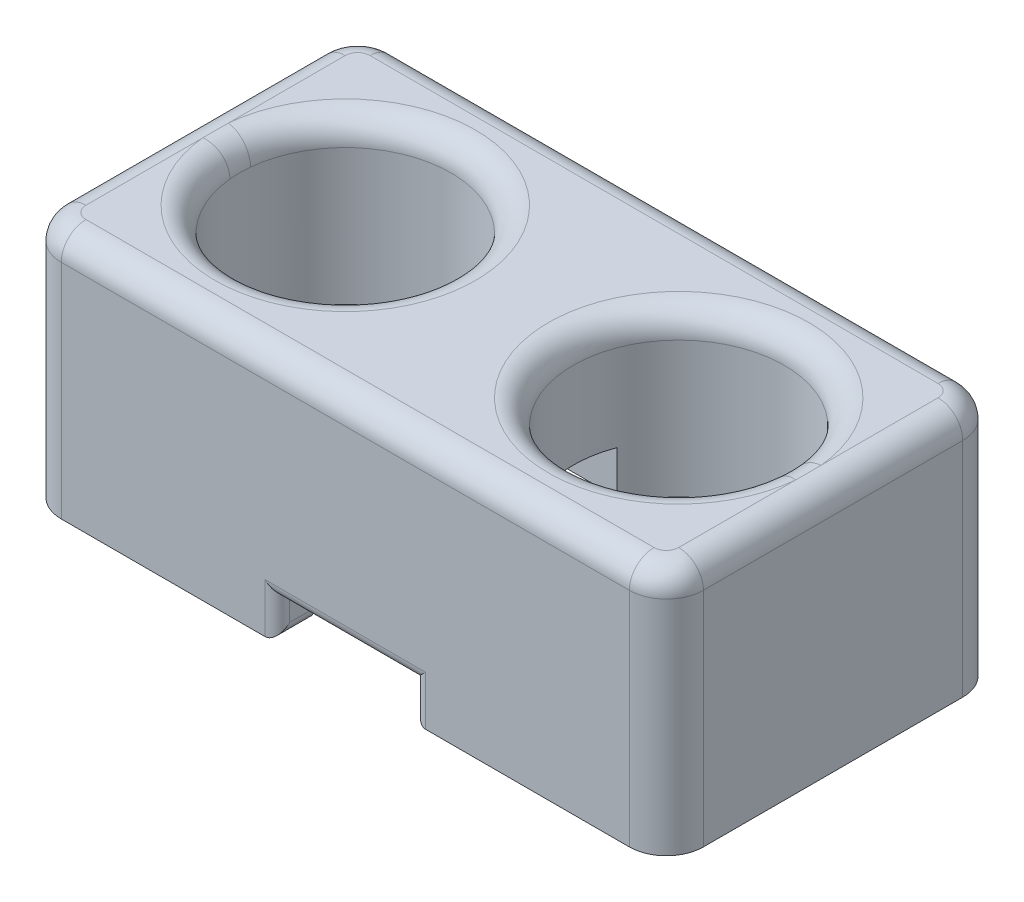
SolidWorks part; units mm, degrees
ref_plane "Front Plane" through (0, 0, 0) normal (0, 0, 1) x (1, 0, 0)
ref_plane "Top Plane" through (0, 0, 0) normal (0, 1, 0) x (1, 0, 0)
ref_plane "Right Plane" through (0, 0, 0) normal (1, 0, 0) x (0, 0, -1)
sketch "Sketch1" plane through (0, 0, 0) normal (0, 1, 0) x (1, 0, 0)
  line L0 (-23, -0.2538) -> (23, -0.2538) construction
  line L1 (-23, -10.7538) -> (23, -10.7538)
  line L2 (-23, -10.7538) -> (-23, 10.2462)
  line L3 (-23, 10.2462) -> (23, 10.2462)
  line L4 (23, -10.7538) -> (23, 10.2462)
  line L5 (0, 10.2462) -> (0, -10.7538) construction
  line L7 (5.5, 10.2462) -> (-5.5, 10.2462)
  line L8 (5.5, 10.2462) -> (5.5, -10.7538)
  line L9 (5.5, -10.7538) -> (-5.5, -10.7538)
  line L10 (-5.5, 10.2462) -> (-5.5, -10.7538)
  line L11 (-26, 13.2462) -> (26, 13.2462)
  line L12 (-26, 13.2462) -> (-26, -13.7538)
  line L13 (-26, -13.7538) -> (26, -13.7538)
  line L14 (26, 13.2462) -> (26, -13.7538)
  line L15 (5.5, -10.7538) -> (-5.5, -10.7538)
  line L16 (5.5, -10.7538) -> (5.5, -13.7538)
  line L17 (5.5, -13.7538) -> (-5.5, -13.7538)
  line L18 (-5.5, -10.7538) -> (-5.5, -13.7538)
  circle A0 centre (-13.5, -0.2538) radius 8.55
  circle A1 centre (13.5, -0.2538) radius 8.55
  point P0 (0, 0)
  dimension "D3" = 17.1
  dimension "D4" = 17.5
  dimension "D10" = 9.5
  dimension "D11" = 9.5
  dimension "D1" = 21
  dimension "D2" = 46
  dimension "D5" = 11
  dimension "D6" = 3
  dimension "D7" = 3
  dimension "D8" = 3
  dimension "D9" = 3
extrude "Boss-Extrude1" add sketch "Sketch1" along normal blind 20 contours L14 L11 L12 L13 L4 L1 L2 L3 | L10 A0 L3 L2 L1 | L3 L10 L1 L8 | L8 A1 L1 L4 L3 | L1 L18 L13 L16 | A0 | A1 region at (-22.7266, 0, 0.2538) region at (-14.25, 0, 11.3397) region at (0, 0, 0.2538) region at (0, 0, 12.2538) region at (5.7734, 0, 7.0123) region at (-13.5805, 0, 0.2538) region at (13.5805, 0, 0.2538)
extrude "Cut-Extrude1" cut sketch "Sketch1<3>" along normal blind 3 contours L1 L18 L13 L16 region at (0, 0, 12.2538)
sketch "Sketch1<3>" plane through (0, 0, 0) normal (0, 1, 0) x (1, 0, 0) same geometry as "Sketch1"
extrude "Cut-Extrude3" cut sketch "Sketch1<4>" along normal blind 7 contours L10 A0 L3 L2 L1 | L8 A1 L1 L4 L3 | L3 L10 L1 L8 | A0 | A1 region at (-22.7266, 0, 0.2538) region at (0, 0, 0.2538) region at (5.7734, 0, 7.0123) region at (-13.5805, 0, 0.2538) region at (13.5805, 0, 0.2538)
sketch "Sketch1<4>" plane through (0, 0, 0) normal (0, 1, 0) x (1, 0, 0) same geometry as "Sketch1"
extrude "Cut-Extrude7" cut sketch "Sketch1<7>" along normal blind 11 contours L3 L10 L1 L8 region at (0, 0, 0.2538)
sketch "Sketch1<7>" plane through (0, 0, 0) normal (0, 1, 0) x (1, 0, 0) same geometry as "Sketch1"
extrude "Cut-Extrude9" cut sketch "Sketch1<9>" along normal through all contours L10 A0 | L8 A1 region at (-13.5805, 0, 0.2538) region at (13.5805, 0, 0.2538)
sketch "Sketch1<9>" plane through (0, 0, 0) normal (0, 1, 0) x (1, 0, 0) same geometry as "Sketch1"
fillet "Fillet1" radius 2 4 edges at (-26, 20, 0.2538) (0, 20, -13.2462) (26, 20, 0.2538) (0, 20, 13.7538)
fillet "Fillet2" radius 2 2 edges at (13.5, 20, 8.8038) (-13.5, 20, 8.8038)
fillet "Fillet3" radius 3 8 edges at (-25.4142, 19.4142, -12.6604) (25.4142, 19.4142, -12.6604) (25.4142, 19.4142, 13.168) (-25.4142, 19.4142, 13.168) (-26, 9, 13.7538) (26, 9, 13.7538) (26, 9, -13.2462) (-26, 9, -13.2462)
fillet "Fillet4" radius 1 6 edges at (5.5, 1.5, 13.7538) (-5.5, 1.5, 13.7538) (0, 3, 13.7538) (0, 3, 10.7538) (-5.5, 0, 12.2538) (5.5, 0, 12.2538)
